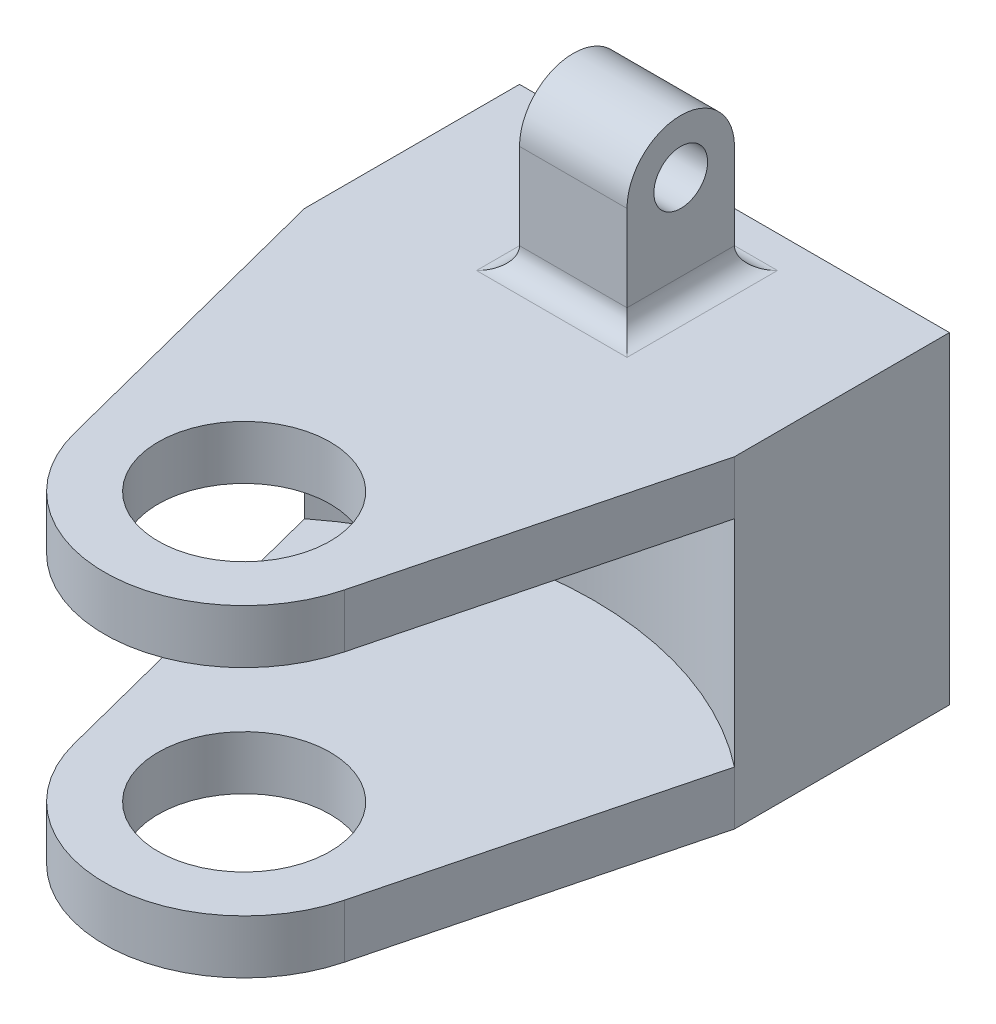
SolidWorks part; units mm, degrees
material "Plain Carbon Steel"
ref_plane "Front" through (0, 0, 0) normal (0, 0, 1) x (1, 0, 0)
ref_plane "Top" through (0, 0, 0) normal (0, 1, 0) x (1, 0, 0)
ref_plane "Right" through (0, 0, 0) normal (1, 0, 0) x (0, 0, -1)
sketch "Sketch1" plane through (0, 0, 0) normal (0, 1, 0) x (1, 0, 0)
  line L0 (-25.4, 32.5341) -> (-15.9912, -4.1063)
  line L1 (-25.4, 32.5341) -> (25.4, 32.5341)
  line L2 (-25.4, 32.5341) -> (-25.4, 57.9341)
  line L3 (-25.4, 57.9341) -> (25.4, 57.9341)
  line L4 (25.4, 32.5341) -> (25.4, 57.9341)
  line L5 (25.4, 32.5341) -> (15.9912, -4.1063)
  circle A0 centre (0, 0) radius 10.16
  circle A1 centre (0, 0) radius 16.51
  circle A2 centre (0, 0) radius 41.275
  dimension "D1" = 20.32
  dimension "D2" = 6.35
  dimension "D3" = 82.55
  dimension "D4" = 50.8
  dimension "D5" = 25.4
extrude "Boss-Extrude1" add sketch "Sketch1" along normal blind 38.1 contours A2 L4 L3 L2 | L1 A2 | A1 L5 L1 L0 | A1 A0 region at (0, 0, -21.9396) region at (0, 0, -36.0643) region at (0, 0, -48.0473) region at (-2.011, 0, -15.9165)
extrude "Cut-Extrude1" cut sketch "Sketch1<3>" along normal blind 25.4 from offset 6.35 contours A1 L5 L1 L0 | L1 A2 | A1 A0 region at (0, 0, -21.9396) region at (0, 0, -36.0643) region at (-2.011, 0, -15.9165)
sketch "Sketch1<3>" plane through (0, 0, 0) normal (0, 1, 0) x (1, 0, 0) same geometry as "Sketch1"
ref_plane "Plane2" through (0, 0, 0) normal (-1, 0, 0) x (0, 0, 1)
sketch "Sketch3" plane through (0, 0, 0) normal (-1, 0, 0) x (0, 0, 1)
  line L0 (-32.5341, 38.1) -> (-57.9341, 38.1) construction
  line L1 (-45.2341, 38.1) -> (-38.8841, 38.1)
  line L2 (-45.2341, 38.1) -> (-45.2341, 30.1082)
  line L3 (-45.2341, 30.1082) -> (-38.8841, 30.1082)
  line L4 (-38.8841, 38.1) -> (-38.8841, 30.1082)
  line L6 (-45.2341, 38.1) -> (-51.5841, 38.1)
  line L7 (-45.2341, 38.1) -> (-45.2341, 30.1082)
  line L8 (-45.2341, 30.1082) -> (-51.5841, 30.1082)
  line L9 (-51.5841, 38.1) -> (-51.5841, 30.1082)
  line L10 (-38.8841, 38.1) -> (-51.5841, 38.1)
  line L11 (-38.8841, 38.1) -> (-38.8841, 50.8)
  line L12 (-38.8841, 50.8) -> (-51.5841, 50.8)
  line L13 (-51.5841, 38.1) -> (-51.5841, 50.8)
  circle A0 centre (-45.2341, 50.8) radius 3.175
  circle A1 centre (-45.2341, 50.8) radius 6.35
  dimension "D4" = 6.35
  dimension "D1" = 6.35
  dimension "D2" = 6.35
  dimension "D3" = 12.7
extrude "Boss-Extrude2" add sketch "Sketch3" along normal blind 6.35 and the other way blind 6.35 contours L12 A1 A0 | L12 A1 A0 | A1 L13 L6 L1 L11 region at (0, 42.0866, -45.2341) region at (0, 44.592, -45.2341) region at (0, 50.942, -40.4716)
sketch "Sketch4" plane through (0, 0, 0) normal (-1, 0, 0) x (0, 0, 1)
  line L0 (-57.9341, 38.1) -> (-57.9341, 0) construction
  line L1 (-57.9341, 19.05) -> (-64.2841, 19.05)
  line L2 (-57.9341, 19.05) -> (-57.9341, 25.4)
  line L3 (-57.9341, 25.4) -> (-64.2841, 25.4)
  line L4 (-64.2841, 19.05) -> (-64.2841, 25.4)
  line L6 (-57.9341, 19.05) -> (-64.2841, 19.05)
  line L7 (-57.9341, 19.05) -> (-57.9341, 12.7)
  line L8 (-57.9341, 12.7) -> (-64.2841, 12.7)
  line L9 (-64.2841, 19.05) -> (-64.2841, 12.7)
  circle A0 centre (-64.2841, 19.05) radius 6.35
  circle A1 centre (-64.2841, 19.05) radius 3.175
  dimension "D4" = 6.35
  dimension "D1" = 6.35
  dimension "D2" = 6.35
  dimension "D3" = 6.35
extrude "Boss-Extrude3" add sketch "Sketch4" along normal blind 6.35 from offset 6.35 contours A1 L4 A0 L9 | A1 L9 A0 L1 | A1 L1 A0 L4 | A0 L8 L7 | A0 L2 L3 region at (0, 15.9058, -61.1399) region at (0, 23.9816, -59.3525) region at (0, 22.1942, -61.1399) region at (0, 14.1184, -59.3525) region at (0, 23.8125, -64.4261)
extrude "Boss-Extrude4" add sketch "Sketch4<3>" against normal blind 6.35 from offset 6.35 contours A1 L1 A0 L4 | A1 L4 A0 L9 | A1 L9 A0 L1 | A0 L2 L3 | A0 L8 L7 region at (0, 15.9058, -61.1399) region at (0, 23.9816, -59.3525) region at (0, 22.1942, -61.1399) region at (0, 14.1184, -59.3525) region at (0, 23.8125, -64.4261) offset against normal yes
sketch "Sketch4<3>" plane through (0, 0, 0) normal (-1, 0, 0) x (0, 0, 1) same geometry as "Sketch4"
fillet "Fillet1" radius 2.54 10 edges at (9.525, 12.7, -57.9341) (9.525, 25.4, -57.9341) (-9.525, 12.7, -57.9341) (-9.525, 25.4, -57.9341) (6.35, 38.1, -45.2341) (-6.35, 38.1, -45.2341) (0, 38.1, -38.8841) (0, 38.1, -51.5841) (-6.35, 19.05, -57.9341) (6.35, 19.05, -57.9341)
